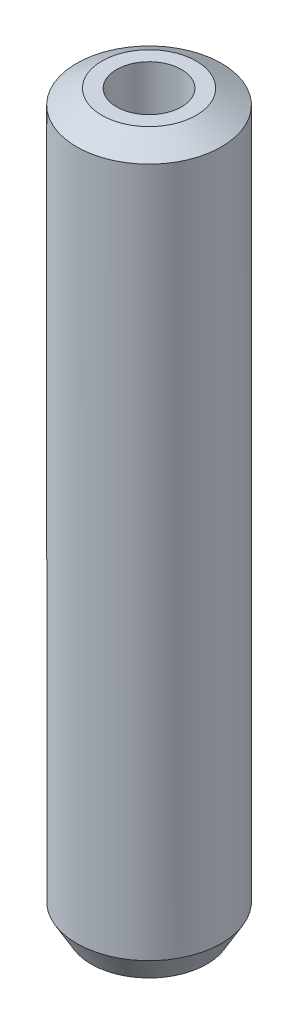
SolidWorks part; units mm, degrees
ref_plane "Front Plane" through (0, 0, 0) normal (0, 0, 1) x (1, 0, 0)
ref_plane "Top Plane" through (0, 0, 0) normal (0, 1, 0) x (1, 0, 0)
ref_plane "Right Plane" through (0, 0, 0) normal (1, 0, 0) x (0, 0, -1)
sketch "Sketch1" plane through (0, 0, 0) normal (0, 1, 0) x (1, 0, 0)
  circle A0 centre (0, 0) radius 20
  dimension "SHAFT_OD" = 40
extrude "Boss-Extrude1" add sketch "Sketch1" along normal blind 201.5487
sketch "Sketch2" plane through (0, 0, 0) normal (0, 1, 0) x (1, 0, 0)
  circle A0 centre (0, 0) radius 8.9625
  dimension "BORE_D" = 17.9251
extrude "Cut-Extrude1" cut sketch "Sketch2" along normal through all
chamfer "Chamfer1" distance 4.0335 angle 60 2 edges at (0, 201.5487, 20) (0, 0, 20) first distance on face at (0, 201.5487, 20) first distance on face at (0, 0, 8.9625)
